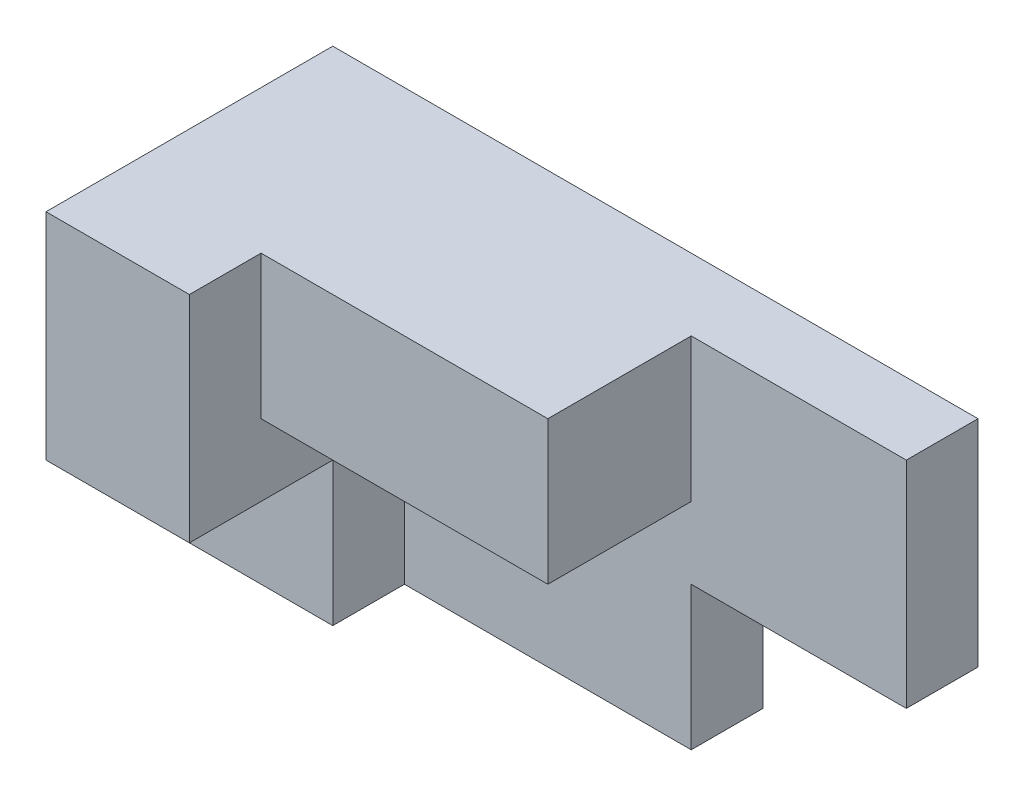
SolidWorks part; units mm, degrees
ref_plane "Front Plane" through (0, 0, 0) normal (0, 0, 1) x (1, 0, 0)
ref_plane "Top Plane" through (0, 0, 0) normal (0, 1, 0) x (1, 0, 0)
ref_plane "Right Plane" through (0, 0, 0) normal (1, 0, 0) x (0, 0, -1)
sketch "Sketch2" plane through (0, 0, 0) normal (0, 0, 1) x (1, 0, 0)
  line L1 (0, 0) -> (60, 0)
  line L2 (0, 0) -> (0, 50)
  line L3 (0, 50) -> (60, 50)
  line L4 (60, 0) -> (60, 50)
  line L5 (60, 50) -> (90, 50)
  line L6 (60, 20) -> (90, 20)
  line L7 (90, 50) -> (90, 20)
  line L16 (20, 20) -> (20, 50)
  line L19 (0, 20) -> (20, 20)
  line L20 (20, 0) -> (20, 20)
  line L21 (20, 30) -> (60, 30)
  dimension "D1" = 60
  dimension "D2" = 50
  dimension "D3" = 30
  dimension "D4" = 30
  dimension "D5" = 20
  dimension "D6" = 20
  dimension "D7" = 20
extrude "Boss-Extrude2" add sketch "Sketch2" along normal blind 10 contours L7 L5 L4 L6 | L16 L21 L4 L3 | L21 L16 L20 L1 L4 | L1 L20 L19 L2 | L2 L19 L16 L3 region at (10, 10, 0) region at (40, 15, 0) region at (10, 35, 0) region at (75, 35, 0) region at (40, 40, 0)
extrude "Boss-Extrude5" add sketch "Sketch2<6>" along normal blind 20 contours L1 L20 L19 L2 region at (10, 10, 0)
sketch "Sketch2<6>" plane through (0, 0, 0) normal (0, 0, 1) x (1, 0, 0) same geometry as "Sketch2"
extrude "Boss-Extrude6" add sketch "Sketch2<7>" along normal blind 30 contours L16 L21 L4 L3 region at (40, 40, 0)
sketch "Sketch2<7>" plane through (0, 0, 0) normal (0, 0, 1) x (1, 0, 0) same geometry as "Sketch2"
extrude "Boss-Extrude7" add sketch "Sketch2<8>" along normal blind 40 contours L2 L19 L16 L3 region at (10, 35, 0)
sketch "Sketch2<8>" plane through (0, 0, 0) normal (0, 0, 1) x (1, 0, 0) same geometry as "Sketch2"
